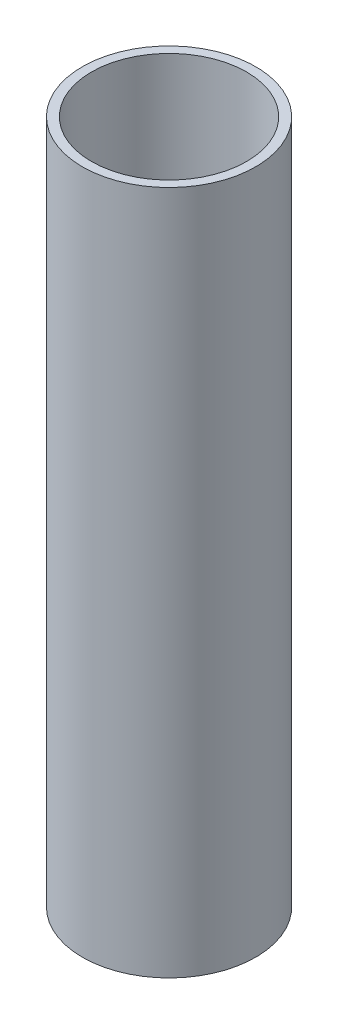
SolidWorks part; units mm, degrees
material "AISI 304"
ref_plane "Спереди" through (0, 0, 0) normal (0, 0, 1) x (1, 0, 0)
ref_plane "Сверху" through (0, 0, 0) normal (0, 1, 0) x (1, 0, 0)
ref_plane "Справа" through (0, 0, 0) normal (1, 0, 0) x (0, 0, -1)
ref_axis "ОсьX" through (-88.99, 0, 0) along (1, 0, 0)
ref_axis "ОсьZ" through (0, 55, 0) along (0, -1, 0)
ref_axis "ОсьY" through (0, 0, -88.99) along (0, 0, 1)
sketch "Эскиз1" plane through (0, 0, 0) normal (0, 0, 1) x (1, 0, 0)
  line L0 (-38, 300) -> (-38, 0)
  line L1 (0, 26.169) -> (0, -22.1581) construction
  dimension "D1" = 76
  dimension "D2" = 300
revolve "Повернуть-Тонкостенный1" add sketch "Эскиз1" angle 360 about L1 wall 4
